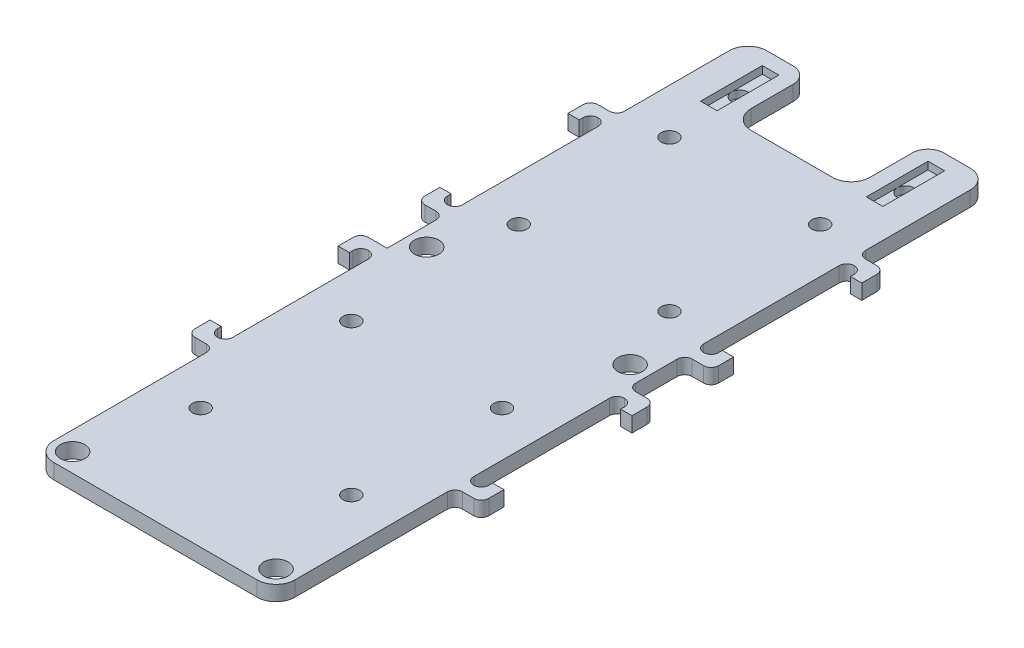
SolidWorks part; units mm, degrees
ref_plane "Front Plane" through (0, 0, 0) normal (0, 0, 1) x (1, 0, 0)
ref_plane "Top Plane" through (0, 0, 0) normal (0, 1, 0) x (1, 0, 0)
ref_plane "Right Plane" through (0, 0, 0) normal (1, 0, 0) x (0, 0, -1)
sketch "Sketch1" plane through (0, 0, 0) normal (0, 1, 0) x (1, 0, 0)
  line L0 (0, 42.225) -> (0, -42.225) construction
  line L1 (16, 42.225) -> (-16, 42.225)
  line L2 (16, 42.225) -> (16, -42.225)
  line L3 (16, -42.225) -> (-16, -42.225)
  line L4 (-16, 42.225) -> (-16, -42.225)
  line L5 (16, 42.225) -> (-16, -42.225) construction
  line L6 (16, -42.225) -> (-16, 42.225) construction
  line L12 (-12.1, 50.425) -> (-12.1, 52.425) construction
  line L17 (-11, 52.425) -> (-11, 42.225) construction
  line L18 (-7.9, 42.225) -> (-14.1, 42.225)
  line L20 (-10, 36) -> (10, 36)
  line L21 (-10, 36) -> (-10, 16)
  line L22 (-10, 16) -> (10, 16)
  line L23 (10, 36) -> (10, 16)
  line L24 (-10, 36) -> (10, 16) construction
  line L25 (-10, 16) -> (10, 36) construction
  line L26 (-14.5, 10.775) -> (14.5, 10.775)
  line L27 (-14.5, 10.775) -> (-14.5, 41.225)
  line L28 (-14.5, 41.225) -> (14.5, 41.225)
  line L29 (14.5, 10.775) -> (14.5, 41.225)
  line L30 (-14.5, 10.775) -> (14.5, 41.225) construction
  line L31 (-14.5, 41.225) -> (14.5, 10.775) construction
  line L32 (-10, -6.225) -> (10, -6.225)
  line L33 (-10, -6.225) -> (-10, -26.225)
  line L34 (-10, -26.225) -> (10, -26.225)
  line L35 (10, -6.225) -> (10, -26.225)
  line L36 (-10, -6.225) -> (10, -26.225) construction
  line L37 (-10, -26.225) -> (10, -6.225) construction
  line L38 (-15.75, -36.225) -> (15.75, -36.225)
  line L39 (-15.75, -36.225) -> (-15.75, 3.775)
  line L40 (-15.75, 3.775) -> (15.75, 3.775)
  line L41 (15.75, -36.225) -> (15.75, 3.775)
  line L42 (-15.75, -36.225) -> (15.75, 3.775) construction
  line L43 (-15.75, 3.775) -> (15.75, -36.225) construction
  line L48 (-7.9, 42.225) -> (-7.9, 52.425)
  line L49 (-7.9, 52.425) -> (-14.1, 52.425)
  line L59 (-14.1, 42.225) -> (-14.1, 52.425)
  line L63 (-12.1, 50.425) -> (-9.9, 50.425)
  line L64 (-12.1, 50.425) -> (-12.1, 42.225)
  line L65 (-12.1, 42.225) -> (-9.9, 42.225)
  line L66 (-9.9, 50.425) -> (-9.9, 42.225)
  line L67 (-12.1, 50.425) -> (-9.9, 42.225) construction
  line L68 (-12.1, 42.225) -> (-9.9, 50.425) construction
  line L69 (-12.1, 50.425) -> (-14.1, 50.425) construction
  line L74 (7.9, 42.225) -> (14.1, 42.225)
  line L75 (14.1, 42.225) -> (14.1, 52.425)
  line L76 (7.9, 52.425) -> (14.1, 52.425)
  line L77 (7.9, 42.225) -> (7.9, 52.425)
  line L78 (12.1, 50.425) -> (9.9, 50.425)
  line L79 (12.1, 50.425) -> (12.1, 42.225)
  line L80 (12.1, 42.225) -> (9.9, 42.225)
  line L81 (9.9, 50.425) -> (9.9, 42.225)
  line L82 (-14.5, 10.775) -> (-14.5, 3.775) construction
  line L83 (-14.5, 7.275) -> (16, 7.275) construction
  line L89 (-13.5, -37.225) -> (-16, -37.225) construction
  line L94 (-14.1, 52.425) -> (-16, 52.425)
  line L95 (-14.1, 52.425) -> (-14.1, 42.225)
  line L96 (-14.1, 42.225) -> (-16, 42.225)
  line L97 (-16, 52.425) -> (-16, 42.225)
  line L98 (14.1, 52.425) -> (16, 52.425)
  line L99 (14.1, 52.425) -> (14.1, 42.225)
  line L100 (14.1, 42.225) -> (16, 42.225)
  line L101 (16, 52.425) -> (16, 42.225)
  circle A3 centre (-10, 36) radius 1.1
  circle A4 centre (10, 36) radius 1.1
  circle A5 centre (10, 16) radius 1.1
  circle A6 centre (-10, 16) radius 1.1
  circle A7 centre (-10, -6.225) radius 1.1
  circle A8 centre (10, -6.225) radius 1.1
  circle A9 centre (10, -26.225) radius 1.1
  circle A10 centre (-10, -26.225) radius 1.1
  circle A37 centre (-13.5, 7.275) radius 2.5
  circle A38 centre (-13.5, 7.275) radius 1.625
  circle A39 centre (13.5, 7.275) radius 1.625
  circle A40 centre (-13.5, -39.725) radius 2.5
  circle A41 centre (-13.5, -39.725) radius 1.625
  circle A42 centre (13.5, -39.725) radius 1.625
  point P0 (0, 0)
  point P8 (0, 0)
  point P16 (0, 26)
  point P26 (0, 26)
  point P31 (0, -16.225)
  point P36 (0, -16.225)
  point P61 (-11, 46.325)
  dimension "D3" = 2
  dimension "D17" = 2.2
  dimension "D22" = 5
  dimension "D23" = 3.25
  dimension "D8" = 32
  dimension "D9" = 22
  dimension "D10" = 20
  dimension "D11" = 29
  dimension "D12" = 30.45
  dimension "D13" = 40
  dimension "D14" = 31.5
  dimension "D15" = 1
  dimension "D16" = 7
  dimension "D18" = 2.2
  dimension "D20" = 8.2
  dimension "D24" = 1
extrude "Base shape" add sketch "Sketch1" along normal blind 2 contours L63 L66 L1 L48 L49 L59 L18 L64 | L81 L78 L79 L1 L75 L76 L77 | L94 L97 L1 L59 | L101 L98 L75 L1 | L1 L4 L3 L2 | A4 | A3 | A7 | A8 | A9 | A10 | A5 | A6 | A39 | A38 | A41 | A42 region at (15.05, 0, -47.325) region at (13.1, 0, -42.3444) region at (-8.9, 0, -42.3444) region at (-15.05, 0, -47.325)
sketch "Sketch2" plane through (0, 0, 0) normal (0, -1, 0) x (1, 0, 0)
  line L0 (-12.1, -42.225) -> (-9.9, -50.425) construction
  line L1 (12.1, -42.225) -> (9.9, -50.425) construction
  line L4 (12.1, -42.225) -> (9.9, -42.225)
  line L5 (12.1, -50.425) -> (12.1, -42.225)
  line L6 (9.9, -50.425) -> (12.1, -50.425)
  line L7 (9.9, -42.225) -> (9.9, -50.425)
  line L8 (12.1, -42.225) -> (9.9, -42.225)
  line L9 (12.1, -50.425) -> (12.1, -42.225)
  line L10 (9.9, -50.425) -> (12.1, -50.425)
  line L11 (9.9, -42.225) -> (9.9, -50.425)
  line L12 (-9.9, -42.225) -> (-12.1, -42.225)
  line L13 (-9.9, -50.425) -> (-9.9, -42.225)
  line L14 (-12.1, -50.425) -> (-9.9, -50.425)
  line L15 (-12.1, -42.225) -> (-12.1, -50.425)
  line L16 (-9.9, -42.225) -> (-12.1, -42.225)
  line L17 (-9.9, -50.425) -> (-9.9, -42.225)
  line L18 (-12.1, -50.425) -> (-9.9, -50.425)
  line L19 (-12.1, -42.225) -> (-12.1, -50.425)
  circle A0 centre (-11, -46.325) radius 1.1
  circle A1 centre (11, -46.325) radius 1.1
  dimension "D1" = 0
  dimension "D2" = 0
extrude "Camera mount pockets" add sketch "Sketch2" against normal offset from surface (1 mm away) 1 contours A0 L19 | A0 L17 | A1 L9 | A1 L11 region at (11, 0, -43.8523) region at (11, 0, -48.7977) region at (-11, 0, -43.8523) region at (-11, 0, -48.7977) up to face at (11, 2, -46.325)
fillet "Main fillets" radius 2.5 6 edges at (7.9, 1, -42.225) (-7.9, 1, -42.225) (-16, 1, -52.425) (16, 1, -52.425) (-16, 1, 42.225) (16, 1, 42.225)
fillet "Inner camera fillets" radius 2.1 2 edges at (-7.9, 1, -52.425) (7.9, 1, -52.425)
sketch "Sketch3" [suppressed] plane through (0, 2, 0) normal (0, 1, 0) x (1, 0, 0)
  line L6 (12.1, 42.225) -> (12.1, 50.425)
  line L7 (9.9, 42.225) -> (12.1, 42.225)
  line L8 (-10, 52.425) -> (-13.5, 52.425)
  line L9 (-16, 49.925) -> (-16, -39.725)
  line L10 (-13.5, -42.225) -> (13.5, -42.225)
  line L11 (16, -39.725) -> (16, 49.925)
  line L12 (13.5, 52.425) -> (10, 52.425)
  line L13 (7.9, 50.325) -> (7.9, 44.725)
  line L14 (5.4, 42.225) -> (-5.4, 42.225)
  line L15 (-7.9, 44.725) -> (-7.9, 50.325)
  line L16 (-10, 52.425) -> (-13.5, 52.425)
  line L17 (-16, 49.925) -> (-16, -39.725)
  line L18 (-13.5, -42.225) -> (13.5, -42.225)
  line L19 (16, -39.725) -> (16, 49.925)
  line L20 (13.5, 52.425) -> (10, 52.425)
  line L21 (7.9, 50.325) -> (7.9, 44.725)
  line L22 (5.4, 42.225) -> (-5.4, 42.225)
  line L23 (-7.9, 44.725) -> (-7.9, 50.325)
  line L24 (9.9, 50.425) -> (9.9, 42.225)
  line L25 (12.1, 50.425) -> (9.9, 50.425)
  line L26 (12.1, 42.225) -> (12.1, 50.425)
  line L27 (9.9, 42.225) -> (12.1, 42.225)
  line L28 (9.9, 50.425) -> (9.9, 42.225)
  line L29 (12.1, 50.425) -> (9.9, 50.425)
  line L30 (-9.9, 42.225) -> (-9.9, 50.425)
  line L31 (-12.1, 42.225) -> (-9.9, 42.225)
  line L32 (-12.1, 50.425) -> (-12.1, 42.225)
  line L33 (-9.9, 50.425) -> (-12.1, 50.425)
  line L34 (-9.9, 42.225) -> (-9.9, 50.425)
  line L35 (-12.1, 42.225) -> (-9.9, 42.225)
  line L36 (-12.1, 50.425) -> (-12.1, 42.225)
  line L37 (-9.9, 50.425) -> (-12.1, 50.425)
  circle A0 centre (13.5, -39.725) radius 1.625 construction
  circle A1 centre (-13.5, -39.725) radius 1.625 construction
  circle A2 centre (-13.5, 7.275) radius 1.625 construction
  circle A3 centre (-10, -6.225) radius 1.1 construction
  circle A4 centre (-10, -26.225) radius 1.1 construction
  circle A5 centre (10, -26.225) radius 1.1 construction
  circle A6 centre (10, -6.225) radius 1.1 construction
  circle A7 centre (13.5, 7.275) radius 1.625 construction
  arc A8 (-13.5, 52.425) -> (-16, 49.925) centre (-13.5, 49.925) ccw
  arc A9 (-16, -39.725) -> (-13.5, -42.225) centre (-13.5, -39.725) ccw
  arc A10 (13.5, -42.225) -> (16, -39.725) centre (13.5, -39.725) ccw
  arc A11 (16, 49.925) -> (13.5, 52.425) centre (13.5, 49.925) ccw
  arc A12 (-7.9, 50.325) -> (-10, 52.425) centre (-10, 50.325) ccw
  arc A13 (5.4, 42.225) -> (7.9, 44.725) centre (5.4, 44.725) ccw
  arc A14 (-7.9, 44.725) -> (-5.4, 42.225) centre (-5.4, 44.725) ccw
  arc A15 (-7.9, 50.325) -> (-10, 52.425) centre (-10, 50.325) ccw
  arc A16 (-13.5, 52.425) -> (-16, 49.925) centre (-13.5, 49.925) ccw
  arc A17 (-16, -39.725) -> (-13.5, -42.225) centre (-13.5, -39.725) ccw
  arc A18 (13.5, -42.225) -> (16, -39.725) centre (13.5, -39.725) ccw
  arc A19 (16, 49.925) -> (13.5, 52.425) centre (13.5, 49.925) ccw
  arc A21 (5.4, 42.225) -> (7.9, 44.725) centre (5.4, 44.725) ccw
  arc A22 (-7.9, 44.725) -> (-5.4, 42.225) centre (-5.4, 44.725) ccw
  circle A24 centre (-10, 16) radius 1.1 construction
  circle A25 centre (-10, 36) radius 1.1 construction
  circle A26 centre (10, 36) radius 1.1 construction
  circle A27 centre (10, 16) radius 1.1 construction
  circle A28 centre (10, 16) radius 1.1
  circle A29 centre (10, 36) radius 1.1
  circle A30 centre (-10, 36) radius 1.1
  circle A31 centre (-10, 16) radius 1.1
  circle A32 centre (13.5, 7.275) radius 1.625
  circle A33 centre (10, -6.225) radius 1.1
  circle A34 centre (10, -26.225) radius 1.1
  circle A35 centre (-10, -26.225) radius 1.1
  circle A36 centre (-10, -6.225) radius 1.1
  circle A37 centre (13.5, -39.725) radius 1.625
  circle A38 centre (-13.5, -39.725) radius 1.625
  circle A39 centre (-13.5, 7.275) radius 1.625
  arc A48 (10, 52.425) -> (7.9, 50.325) centre (10, 50.325) ccw
  arc A49 (10, 52.425) -> (7.9, 50.325) centre (10, 50.325) ccw
  dimension "D1" = 0
  dimension "D2" = 0
  dimension "D3" = 0
extrude "Boss-Extrude3" [suppressed] add sketch "Sketch3" along normal blind 1
sketch "Sketch4" [suppressed] plane through (0, 0, 0) normal (0, -1, 0) x (1, 0, 0)
  line L0 (0, 13.9568) -> (0, -8.6953) construction
  line L1 (-14.1, -38.5) -> (-5.9, -38.5)
  line L2 (-14.1, -38.5) -> (-14.1, -41.7)
  line L3 (-14.1, -41.7) -> (-5.9, -41.7)
  line L4 (-5.9, -38.5) -> (-5.9, -41.7)
  line L5 (-10, -38.5) -> (-10, -41.7) construction
  line L7 (14.1, -38.5) -> (5.9, -38.5)
  line L8 (14.1, -38.5) -> (14.1, -41.7)
  line L9 (14.1, -41.7) -> (5.9, -41.7)
  line L10 (5.9, -38.5) -> (5.9, -41.7)
  line L11 (-14.1, -38.5) -> (-10.9, -41.7) construction
  line L12 (-14.1, -40.1) -> (-5.9, -40.1) construction
  circle A0 centre (-10, -36) radius 2
  circle A1 centre (-13.3929, -39.2071) radius 1
  circle A2 centre (-13.3929, -40.9929) radius 1
  circle A3 centre (-6.6071, -39.2071) radius 1
  circle A4 centre (-6.6071, -40.9929) radius 1
  circle A5 centre (6.6071, -40.9929) radius 1
  circle A6 centre (6.6071, -39.2071) radius 1
  circle A7 centre (13.3929, -39.2071) radius 1
  circle A8 centre (13.3929, -40.9929) radius 1
  point P9 (-10, -38)
  dimension "D5" = 4
  dimension "D7" = 2
  dimension "D1" = 8.2
  dimension "D2" = 3.2
  dimension "D3" = 10
  dimension "D4" = 0.5
  dimension "D6" = 45
extrude "Cut-Extrude1" [suppressed] cut sketch "Sketch4" against normal offset from surface (2 mm away) 1 contours A2 L2 | A2 L3 | L2 A1 | L1 A1 | A3 L4 | A3 L1 | L4 A4 | L3 A4 | A5 L9 | A5 L10 | L10 A6 | L7 A6 | A7 L7 | A7 L8 | L8 A8 | L9 A8 | L3 L4 L1 L2 | L9 L10 L7 L8 up to face at (11, 0, -47.425)
sketch "Sketch5" [suppressed] plane through (0, 2, 0) normal (0, -1, 0) x (1, 0, 0)
  line L0 (-10, -38.5) -> (-10, -41.7) construction
  line L1 (-12.6858, -38.5) -> (-7.3142, -38.5) construction
  line L2 (-12.6858, -41.7) -> (-7.3142, -41.7) construction
  line L3 (0, 5.9884) -> (0, -5.6723) construction
  circle A0 centre (-10, -40.1) radius 1.1
  circle A1 centre (10, -40.1) radius 1.1
  dimension "D1" = 2.2
extrude "Cut-Extrude2" [suppressed] cut sketch "Sketch5" against normal up to next
sketch "Sketch6" plane through (0, 0, 0) normal (0, -1, 0) x (1, 0, 0)
  line L0 (0, -5.1) -> (0, 9.653) construction
  line L1 (13.5, 42.225) -> (-13.5, 42.225) construction
  line L2 (-15.5, -38.775) -> (15.5, -38.775)
  line L3 (-15.5, -38.775) -> (-15.5, 22.225)
  line L4 (-15.5, 22.225) -> (15.5, 22.225)
  line L5 (15.5, -38.775) -> (15.5, 22.225)
  line L6 (-15.5, -38.775) -> (15.5, 22.225) construction
  line L7 (-15.5, 22.225) -> (15.5, -38.775) construction
  line L8 (-15.5, -8.275) -> (15.5, -8.275) construction
  line L9 (-15.5, -8.275) -> (15.5, -38.775) construction
  line L10 (-16, -23.525) -> (16, -23.525) construction
  line L11 (-16, -49.925) -> (-16, 39.725) construction
  line L12 (16, -49.925) -> (16, 39.725) construction
  line L13 (18, -32.025) -> (19.5, -32.025)
  line L14 (16, -35.025) -> (19.5, -35.025)
  line L15 (16, -35.025) -> (16, -12.025)
  line L16 (16, -12.025) -> (19.5, -12.025)
  line L17 (19.5, -35.025) -> (19.5, -12.025)
  line L18 (16, -35.025) -> (19.5, -12.025) construction
  line L19 (16, -12.025) -> (19.5, -35.025) construction
  line L20 (16, -33.525) -> (18, -33.525)
  line L21 (16, -33.525) -> (16, -13.525)
  line L22 (16, -13.525) -> (18, -13.525)
  line L23 (18, -33.525) -> (18, -13.525)
  line L24 (16, -33.525) -> (18, -13.525) construction
  line L25 (16, -13.525) -> (18, -33.525) construction
  line L26 (18, -15.025) -> (19.5, -15.025)
  line L27 (-18, -32.025) -> (-19.5, -32.025)
  line L28 (-18, -15.025) -> (-19.5, -15.025)
  line L29 (-16, -33.525) -> (-16, -13.525)
  line L30 (-16, -33.525) -> (-18, -33.525)
  line L31 (-18, -33.525) -> (-18, -13.525)
  line L32 (-16, -13.525) -> (-18, -13.525)
  line L33 (-16, -35.025) -> (-16, -12.025)
  line L34 (-16, -35.025) -> (-19.5, -35.025)
  line L35 (-19.5, -35.025) -> (-19.5, -12.025)
  line L36 (-16, -12.025) -> (-19.5, -12.025)
  line L37 (16, 18.475) -> (19.5, 18.475)
  line L38 (16, 18.475) -> (16, -4.525)
  line L39 (16, -4.525) -> (19.5, -4.525)
  line L40 (19.5, 18.475) -> (19.5, -4.525)
  line L41 (16, 16.975) -> (18, 16.975)
  line L42 (16, 16.975) -> (16, -3.025)
  line L43 (16, -3.025) -> (18, -3.025)
  line L44 (18, 16.975) -> (18, -3.025)
  line L45 (18, -1.525) -> (19.5, -1.525)
  line L46 (18, 15.475) -> (19.5, 15.475)
  line L47 (-18, 15.475) -> (-19.5, 15.475)
  line L48 (-18, -1.525) -> (-19.5, -1.525)
  line L49 (-16, 16.975) -> (-16, -3.025)
  line L50 (-16, 16.975) -> (-18, 16.975)
  line L51 (-18, 16.975) -> (-18, -3.025)
  line L52 (-16, -3.025) -> (-18, -3.025)
  line L53 (-16, 18.475) -> (-16, -4.525)
  line L54 (-16, 18.475) -> (-19.5, 18.475)
  line L55 (-19.5, 18.475) -> (-19.5, -4.525)
  line L56 (-16, -4.525) -> (-19.5, -4.525)
  point P1 (0, -8.275)
  point P12 (0, -23.525)
  point P19 (17.75, -23.525)
  point P25 (17, -23.525)
  dimension "D1" = 61
  dimension "D2" = 31
  dimension "D3" = 20
  dimension "D4" = 23
  dimension "D5" = 3.5
  dimension "D6" = 2
  dimension "D7" = 20
  dimension "D8" = 1.5
extrude "Strap holders" add sketch "Sketch6" against normal up to surface (2 mm away) contours L23 L20 L14 L17 L13 | L23 L26 L17 L16 L22 | L45 L44 L43 L39 L40 | L44 L46 L40 L37 L38 L41 | L54 L55 L47 L51 L50 | L56 L52 L51 L48 L55 | L36 L35 L28 L31 L32 | L35 L34 L30 L31 L27 region at (18.05, 0, -33.825) region at (18.05, 0, -13.225) region at (-18.05, 0, -33.825) region at (-18.05, 0, -13.225) region at (18.05, 0, 17.275) region at (18.05, 0, -3.325) region at (-18.05, 0, 17.275) region at (-18.05, 0, -3.325) up to face at (11, 2, -46.325)
fillet "Strap holder fillets" radius 1 31 edges at (19.5, 1, -35.025) (19.5, 1, -12.025) (-19.5, 1, 18.475) (-19.5, 1, -4.525) (-19.5, 1, -35.025) (-19.5, 1, -12.025) (-18, 1, -33.525) (-18, 1, -3.025) (-16, 1, -33.525) (-16, 1, -12.025) (-16, 1, -3.025) (-16, 1, 18.475) (-16, 1, 16.975) (-16, 1, -13.525) (-16, 1, -35.025) (16, 1, -3.025) (18, 1, -3.025) (18, 1, -13.525) (18, 1, -33.525) (16, 1, -33.525) (16, 1, -12.025) (16, 1, -35.025) (-18, 1, -13.525) (-18, 1, 16.975) (16, 1, -13.525) (16, 1, -4.525) (19.5, 1, -4.525) (18, 1, 16.975) (16, 1, 16.975) (19.5, 1, 18.475) (16, 1, 18.475)
